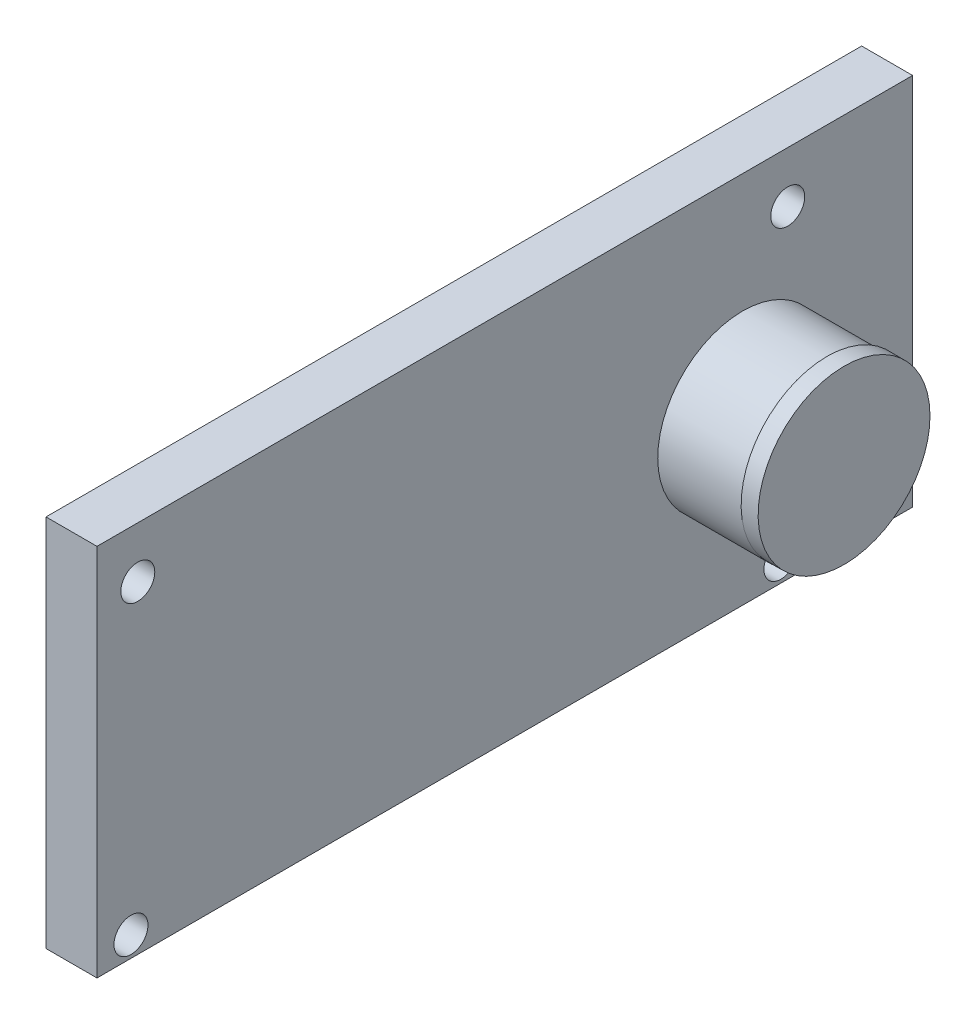
SolidWorks part; units mm, degrees
ref_plane "Front Plane" through (0, 0, 0) normal (0, 0, 1) x (1, 0, 0)
ref_plane "Top Plane" through (0, 0, 0) normal (0, 1, 0) x (1, 0, 0)
ref_plane "Right Plane" through (0, 0, 0) normal (1, 0, 0) x (0, 0, -1)
sketch "Sketch1" plane through (0, 0, 0) normal (1, 0, 0) x (0, 0, -1)
  line L1 (0, 0) -> (48, 0)
  line L2 (0, 0) -> (0, 22)
  line L3 (0, 22) -> (48, 22)
  line L4 (48, 0) -> (48, 22)
  line L5 (0, 0) -> (48, 22) construction
  line L6 (0, 22) -> (48, 0) construction
  circle A0 centre (38, 9.9955) radius 5
  circle A1 centre (40.65, 18.9955) radius 1
  circle A2 centre (2.4, 18.9955) radius 1
  circle A3 centre (2, 1.2) radius 1
  circle A4 centre (40.25, 1.2) radius 1
  point P4 (24, 11)
  point P16 (0, 0)
  dimension "D2" = 2
  dimension "D3" = 2
  dimension "D4" = 10
  dimension "D14" = 2
  dimension "D15" = 2
  dimension "D1" = 38.25
  dimension "D5" = 9
  dimension "D6" = 48
  dimension "D7" = 2.4
  dimension "D8" = 38
  dimension "D9" = 22
  dimension "D10" = 17.8
  dimension "D11" = 17.8
  dimension "D12" = 38.25
  dimension "D13" = 1.2
  dimension "D16" = 1.2
extrude "Boss-Extrude1" add sketch "Sketch1" along normal blind 3
extrude "Boss-Extrude2" add sketch "Sketch1<2>" along normal blind 8 contours A0
sketch "Sketch1<2>" plane through (0, 0, 0) normal (1, 0, 0) x (0, 0, -1) same geometry as "Sketch1"
sketch "Sketch2" plane through (0, 0, 0) normal (-1, 0, 0) x (0, 0, 1)
  line L1 (-17.2529, 17.8732) -> (-15.1486, 17.8732)
  line L2 (-17.2529, 17.8732) -> (-17.2529, 16.8644)
  line L3 (-17.2529, 16.8644) -> (-15.1486, 16.8644)
  line L4 (-15.1486, 17.8732) -> (-15.1486, 16.8644)
  line L5 (-17.2529, 17.8732) -> (-15.1486, 16.8644) construction
  line L6 (-17.2529, 16.8644) -> (-15.1486, 17.8732) construction
  line L7 (-13.2499, 17.8732) -> (-11.4171, 17.8732)
  line L8 (-13.2499, 17.8732) -> (-13.2499, 16.8644)
  line L9 (-13.2499, 16.8644) -> (-11.4171, 16.8644)
  line L10 (-11.4171, 17.8732) -> (-11.4171, 16.8644)
  line L11 (-13.2499, 17.8732) -> (-11.4171, 16.8644) construction
  line L12 (-13.2499, 16.8644) -> (-11.4171, 17.8732) construction
  line L13 (-8.9401, 17.8732) -> (-6.852, 17.8732)
  line L14 (-8.9401, 17.8732) -> (-8.9401, 16.8644)
  line L15 (-8.9401, 16.8644) -> (-6.852, 16.8644)
  line L16 (-6.852, 17.8732) -> (-6.852, 16.8644)
  line L17 (-8.9401, 17.8732) -> (-6.852, 16.8644) construction
  line L18 (-8.9401, 16.8644) -> (-6.852, 17.8732) construction
  line L19 (-15.6447, 9.1836) -> (-11.4171, 9.1836)
  line L20 (-15.6447, 9.1836) -> (-15.6447, 7.9091)
  line L21 (-15.6447, 7.9091) -> (-11.4171, 7.9091)
  line L22 (-11.4171, 9.1836) -> (-11.4171, 7.9091)
  line L23 (-15.6447, 9.1836) -> (-11.4171, 7.9091) construction
  line L24 (-15.6447, 7.9091) -> (-11.4171, 9.1836) construction
  line L25 (-6.2836, 8.5464) -> (-2.9228, 8.5464)
  line L26 (-6.2836, 8.5464) -> (-6.2836, 7.0742)
  line L27 (-6.2836, 7.0742) -> (-2.9228, 7.0742)
  line L28 (-2.9228, 8.5464) -> (-2.9228, 7.0742)
  line L29 (-6.2836, 8.5464) -> (-2.9228, 7.0742) construction
  line L30 (-6.2836, 7.0742) -> (-2.9228, 8.5464) construction
  line L31 (-27.4768, 2.6789) -> (-26.7324, 2.6789)
  line L32 (-27.4768, 2.6789) -> (-27.4768, 4.712)
  line L33 (-27.4768, 4.712) -> (-26.7324, 4.712)
  line L34 (-26.7324, 2.6789) -> (-26.7324, 4.712)
  line L35 (-27.4768, 2.6789) -> (-26.7324, 4.712) construction
  line L36 (-27.4768, 4.712) -> (-26.7324, 2.6789) construction
  line L37 (-29.8808, 2.6789) -> (-29.0447, 2.6789)
  line L38 (-29.8808, 2.6789) -> (-29.8808, 4.712)
  line L39 (-29.8808, 4.712) -> (-29.0447, 4.712)
  line L40 (-29.0447, 2.6789) -> (-29.0447, 4.712)
  line L41 (-29.8808, 2.6789) -> (-29.0447, 4.712) construction
  line L42 (-29.8808, 4.712) -> (-29.0447, 2.6789) construction
  line L43 (-33.0291, 2.6789) -> (-31.9344, 2.6789)
  line L44 (-33.0291, 2.6789) -> (-33.0291, 4.712)
  line L45 (-33.0291, 4.712) -> (-31.9344, 4.712)
  line L46 (-31.9344, 2.6789) -> (-31.9344, 4.712)
  line L47 (-33.0291, 2.6789) -> (-31.9344, 4.712) construction
  line L48 (-33.0291, 4.712) -> (-31.9344, 2.6789) construction
  line L49 (-31.9344, 14.4348) -> (-21.7946, 14.4348)
  line L50 (-31.9344, 14.4348) -> (-31.9344, 10.741)
  line L51 (-31.9344, 10.741) -> (-21.7946, 10.741)
  line L52 (-21.7946, 14.4348) -> (-21.7946, 10.741)
  line L53 (-31.9344, 14.4348) -> (-21.7946, 10.741) construction
  line L54 (-31.9344, 10.741) -> (-21.7946, 14.4348) construction
  line L55 (-47.115, 10.741) -> (-46.0696, 10.741)
  line L56 (-47.115, 10.741) -> (-47.115, 9.1836)
  line L57 (-47.115, 9.1836) -> (-46.0696, 9.1836)
  line L58 (-46.0696, 10.741) -> (-46.0696, 9.1836)
  line L59 (-47.115, 10.741) -> (-46.0696, 9.1836) construction
  line L60 (-47.115, 9.1836) -> (-46.0696, 10.741) construction
  line L61 (-46.5923, 5.8932) -> (-45.3731, 5.8932)
  line L62 (-46.5923, 5.8932) -> (-46.5923, 3.6955)
  line L63 (-46.5923, 3.6955) -> (-45.3731, 3.6955)
  line L64 (-45.3731, 5.8932) -> (-45.3731, 3.6955)
  line L65 (-46.5923, 5.8932) -> (-45.3731, 3.6955) construction
  line L66 (-46.5923, 3.6955) -> (-45.3731, 5.8932) construction
  line L67 (-45.9827, 2.6789) -> (-47.115, 2.6789)
  line L68 (-45.9827, 2.6789) -> (-45.9827, 1.376)
  line L69 (-45.9827, 1.376) -> (-47.115, 1.376)
  line L70 (-47.115, 2.6789) -> (-47.115, 1.376)
  line L71 (-45.9827, 2.6789) -> (-47.115, 1.376) construction
  line L72 (-45.9827, 1.376) -> (-47.115, 2.6789) construction
  circle A0 centre (-15.6447, 4.712) radius 1.4737
  circle A1 centre (-6.852, 2.6789) radius 1.303
  point P4 (-16.2007, 17.3688)
  point P9 (-12.3335, 17.3688)
  point P14 (-7.896, 17.3688)
  point P19 (-13.5309, 8.5464)
  point P24 (-4.6032, 7.8103)
  point P29 (-27.1046, 3.6955)
  point P34 (-29.4627, 3.6955)
  point P39 (-32.4818, 3.6955)
  point P48 (-26.8645, 12.5879)
  point P53 (-46.5923, 9.9623)
  point P58 (-45.9827, 4.7944)
  point P63 (-46.5489, 2.0274)
extrude "Boss-Extrude3" add sketch "Sketch2" along normal blind 0.5 contours L13 L16 L15 L14 | L7 L10 L9 L8 | L1 L4 L3 L2 | L40 L39 L38 L37 | L32 L33 L34 L31 | L45 L46 L43 L44
extrude "Boss-Extrude4" add sketch "Sketch2<3>" along normal blind 0.8 contours L58 L57 L56 L55 | L61 L64 L63 L62 | L67 L70 L69 L68 | L21 L22 L19 L20 | L27 L28 L25 L26
sketch "Sketch2<3>" plane through (0, 0, 0) normal (-1, 0, 0) x (0, 0, 1) same geometry as "Sketch2"
extrude "Boss-Extrude5" add sketch "Sketch2<4>" along normal blind 1.2 contours L49 L52 L51 L50
sketch "Sketch2<4>" plane through (0, 0, 0) normal (-1, 0, 0) x (0, 0, 1) same geometry as "Sketch2"
extrude "Boss-Extrude6" add sketch "Sketch2<5>" along normal blind 1.5 contours A1 | A0 region at (0, 2.6789, -6.852)
sketch "Sketch2<5>" plane through (0, 0, 0) normal (-1, 0, 0) x (0, 0, 1) same geometry as "Sketch2"
sketch "Sketch4" plane through (8, 0, 0) normal (1, 0, 0) x (0, 0, -1)
  circle A0 centre (37.9643, 10.1426) radius 5.0573
extrude "Boss-Extrude7" add sketch "Sketch4" along normal blind 1
